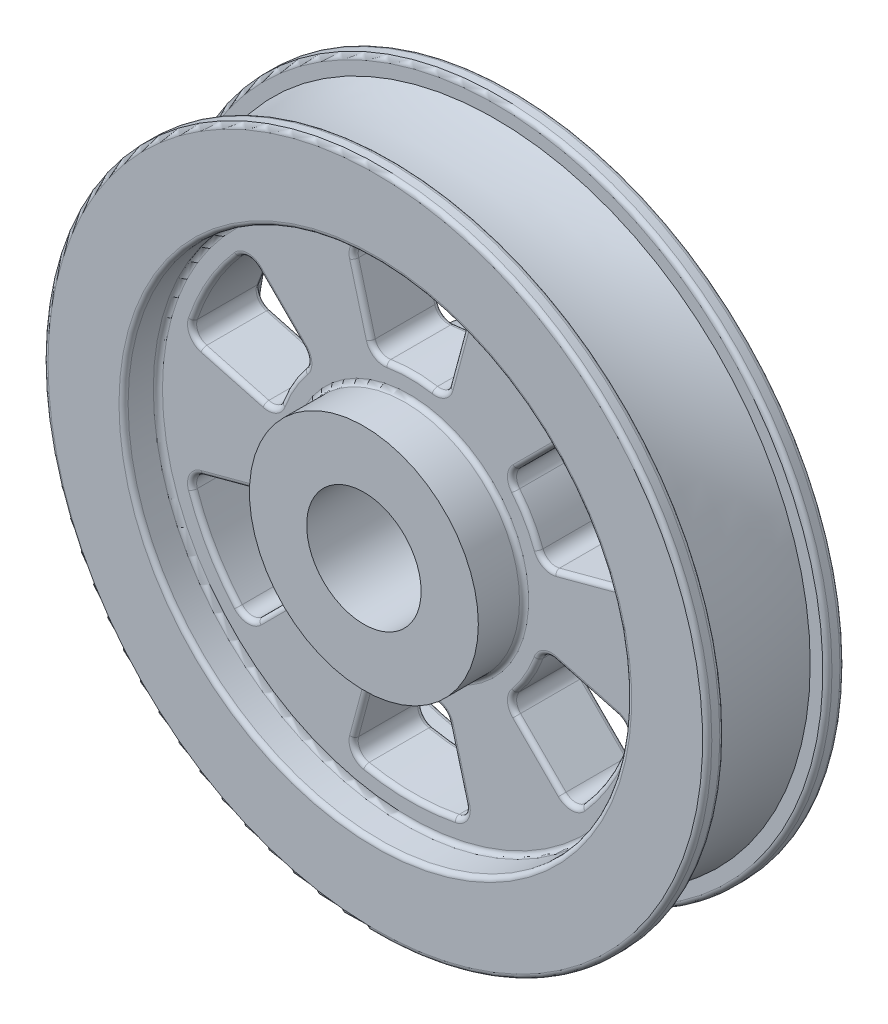
SolidWorks part; units mm, degrees
material "Cast Alloy Steel"
ref_plane "Front Plane" through (0, 0, 0) normal (0, 0, 1) x (1, 0, 0)
ref_plane "Top Plane" through (0, 0, 0) normal (0, 1, 0) x (1, 0, 0)
ref_plane "Right Plane" through (0, 0, 0) normal (1, 0, 0) x (0, 0, -1)
sketch "Wheel Cross-section" plane through (0, 0, 0) normal (1, 0, 0) x (0, 0, -1)
  line L0 (-130.7747, 0) -> (134.6553, 0) construction
  line L1 (44.45, 31.75) -> (44.45, 63.5)
  line L2 (44.45, 63.5) -> (19.05, 63.5)
  line L3 (19.05, 63.5) -> (19.05, 139.7)
  line L4 (19.05, 139.7) -> (38.1, 139.7)
  line L5 (38.1, 139.7) -> (38.1, 184.15)
  line L6 (38.1, 184.15) -> (28.575, 184.15)
  line L7 (28.575, 184.15) -> (28.575, 174.625)
  line L9 (-28.575, 174.625) -> (-28.575, 184.15)
  line L10 (-28.575, 184.15) -> (-38.1, 184.15)
  line L11 (-38.1, 184.15) -> (-38.1, 139.7)
  line L12 (-38.1, 139.7) -> (-19.05, 139.7)
  line L13 (-19.05, 139.7) -> (-19.05, 63.5)
  line L14 (-19.05, 63.5) -> (-44.45, 63.5)
  line L15 (-44.45, 63.5) -> (-44.45, 31.75)
  line L17 (-44.45, 31.75) -> (44.45, 31.75)
  arc A0 (28.575, 174.625) -> (-28.575, 174.625) centre (0, 324.3221) cw
  dimension "D13" = 152.4
  dimension "D14" = 9.525
  dimension "D1" = 44.45
  dimension "D2" = 88.9
  dimension "D3" = 25.4
  dimension "D4" = 38.1
  dimension "D5" = 63.5
  dimension "D6" = 76.2
  dimension "D7" = 9.525
  dimension "D8" = 9.525
  dimension "D9" = 31.75
  dimension "D10" = 6.35
  dimension "D11" = 139.7
  dimension "D12" = 184.15
revolve "Revolve1" add sketch "Wheel Cross-section" angle 360 about L0
sketch "Spoke cut-out" plane through (0, 0, 19.05) normal (0, 0, 1) x (1, 0, 0)
  line L0 (0, 0) -> (-60.1063, 224.3199) construction
  line L1 (0, 0) -> (0, 216.2459) construction
  line L2 (0, 0) -> (59.3665, 221.5588) construction
  line L3 (30.8348, 115.0771) -> (21.6044, 80.6286)
  line L4 (-30.8348, 115.0771) -> (-21.6044, 80.6286)
  circle A0 centre (0, 0) radius 127 construction
  circle A1 centre (0, 0) radius 76.2 construction
  arc A2 (24.9728, 124.5205) -> (-24.9728, 124.5205) centre (0, 0) ccw
  arc A3 (12.9491, 75.0917) -> (-12.9491, 75.0917) centre (0, 0) ccw
  arc A4 (24.9728, 124.5205) -> (30.8348, 115.0771) centre (23.4745, 117.0493) cw
  arc A5 (-24.9728, 124.5205) -> (-30.8348, 115.0771) centre (-23.4745, 117.0493) ccw
  arc A6 (-12.9491, 75.0917) -> (-21.6044, 80.6286) centre (-14.244, 82.6008) cw
  arc A7 (12.9491, 75.0917) -> (21.6044, 80.6286) centre (14.244, 82.6008) ccw
  point P13 (32.87, 122.6726)
  point P16 (-32.87, 122.6726)
  point P19 (-19.722, 73.6035)
  point P22 (19.722, 73.6035)
  dimension "D1" = 254
  dimension "D2" = 152.4
  dimension "D5" = 7.62
  dimension "D6" = 7.62
  dimension "D7" = 7.62
  dimension "D3" = 15
  dimension "D4" = 15
extrude "Spoke hole" cut sketch "Spoke cut-out" against normal through all
pattern_circular "Spoke hole pattern" count 6 over 360 about axis through (0, 0, 130.7747) along (0, 0, -1) of "Spoke hole" reverse direction yes
fillet "0.10 inch Fillets & Rounds" radius 2.54 106 edges at (-89.8737, -86.4702, -19.05) (-109.9852, -63.5, -19.05) (-119.8223, -34.5978, -19.05) (-97.8529, -26.2196, -19.05) (-75.1507, -22.1991, -19.05) (-65.9911, -38.1, -19.05) (-56.8003, -53.9828, -19.05) (-18.3504, -76.1819, -19.05) (0, -76.2, -19.05) (18.3504, -76.1819, -19.05) (26.2196, -97.8529, -19.05) (29.9485, -121.0681, -19.05) (0, -127, -19.05) (-29.9485, -121.0681, -19.05) (119.8223, -34.5978, -19.05) (109.9852, -63.5, -19.05) (89.8737, -86.4702, -19.05) (71.6333, -71.6333, -19.05) (56.8003, -53.9828, -19.05) (65.9911, -38.1, -19.05) (75.1507, -22.1991, -19.05) (89.8737, 86.4702, -19.05) (109.9852, 63.5, -19.05) (119.8223, 34.5978, -19.05) (97.8529, 26.2196, -19.05) (75.1507, 22.1991, -19.05) (65.9911, 38.1, -19.05) (56.8003, 53.9828, -19.05) (-29.9485, 121.0681, -19.05) (0, 127, -19.05) (29.9485, 121.0681, -19.05) (26.2196, 97.8529, -19.05) (18.3504, 76.1819, -19.05) (0, 76.2, -19.05) (-18.3504, 76.1819, -19.05) (-119.8223, 34.5978, -19.05) (-109.9852, 63.5, -19.05) (-89.8737, 86.4702, -19.05) (-71.6333, 71.6333, -19.05) (-56.8003, 53.9828, -19.05) (-65.9911, 38.1, -19.05) (-75.1507, 22.1991, -19.05) (18.3504, 76.1819, 19.05) (0, 76.2, 19.05) (-18.3504, 76.1819, 19.05) (-26.2196, 97.8529, 19.05) (-29.9485, 121.0681, 19.05) (0, 127, 19.05) (29.9485, 121.0681, 19.05) (75.1507, 22.1991, 19.05) (65.9911, 38.1, 19.05) (56.8003, 53.9828, 19.05) (71.6333, 71.6333, 19.05) (89.8737, 86.4702, 19.05) (109.9852, 63.5, 19.05) (119.8223, 34.5978, 19.05) (56.8003, -53.9828, 19.05) (65.9911, -38.1, 19.05) (75.1507, -22.1991, 19.05) (97.8529, -26.2196, 19.05) (119.8223, -34.5978, 19.05) (109.9852, -63.5, 19.05) (89.8737, -86.4702, 19.05) (-18.3504, -76.1819, 19.05) (0, -76.2, 19.05) (18.3504, -76.1819, 19.05) (26.2196, -97.8529, 19.05) (29.9485, -121.0681, 19.05) (0, -127, 19.05) (-29.9485, -121.0681, 19.05) (-119.8223, -34.5978, 19.05) (-97.8529, -26.2196, 19.05) (-75.1507, -22.1991, 19.05) (-65.9911, -38.1, 19.05) (-56.8003, -53.9828, 19.05) (-71.6333, -71.6333, 19.05) (-89.8737, -86.4702, 19.05) (-89.8737, 86.4702, 19.05) (-71.6333, 71.6333, 19.05) (-56.8003, 53.9828, 19.05) (-65.9911, 38.1, 19.05) (-75.1507, 22.1991, 19.05) (-97.8529, 26.2196, 19.05) (-119.8223, 34.5978, 19.05) (184.15, 0, -28.575) (184.15, 0, 28.575) (184.15, 0, 38.1) (184.15, 0, -38.1) (139.7, 0, -38.1) (139.7, 0, 38.1) (139.7, 0, -19.05) (-71.6333, -71.6333, -19.05) (-26.2196, -97.8529, -19.05) (97.8529, -26.2196, -19.05) (71.6333, 71.6333, -19.05) (-26.2196, 97.8529, -19.05) (-97.8529, 26.2196, -19.05) (63.5, 0, -19.05) (139.7, 0, 19.05) (63.5, 0, 19.05) (26.2196, 97.8529, 19.05) (97.8529, 26.2196, 19.05) (71.6333, -71.6333, 19.05) (-26.2196, -97.8529, 19.05) (-109.9852, -63.5, 19.05) (-109.9852, 63.5, 19.05)
